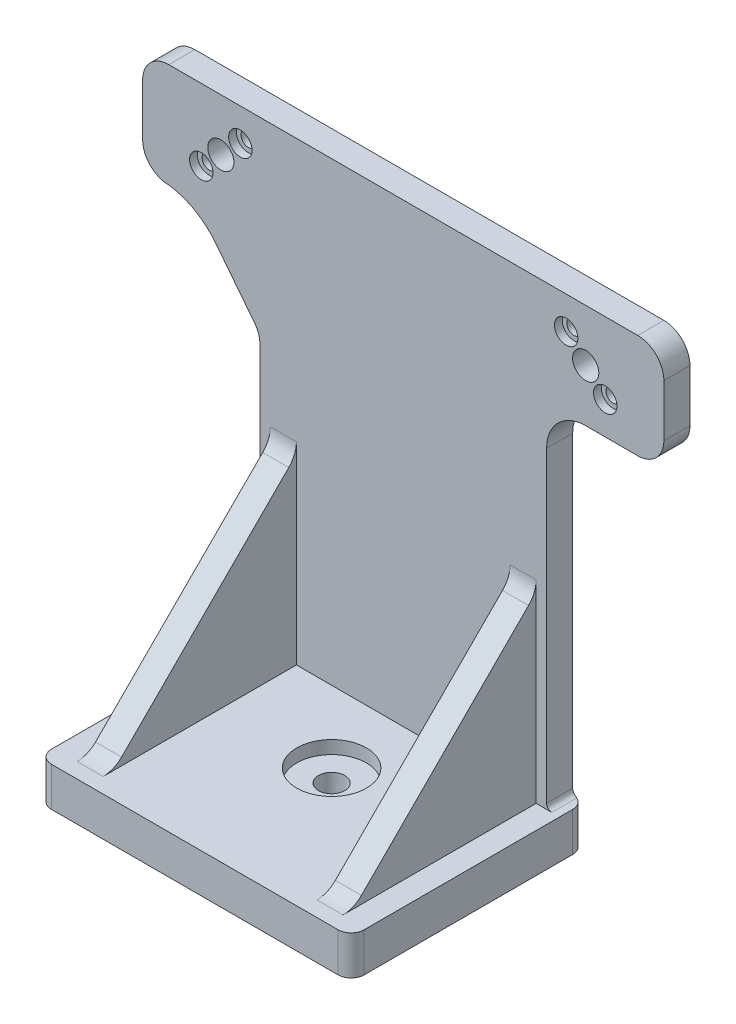
SolidWorks part; units mm, degrees
ref_plane "Ebene vorne" through (0, 0, 0) normal (0, 0, 1) x (1, 0, 0)
ref_plane "Ebene oben" through (0, 0, 0) normal (0, 1, 0) x (1, 0, 0)
ref_plane "Ebene rechts" through (0, 0, 0) normal (1, 0, 0) x (0, 0, -1)
sketch "Skizze1" plane through (0, 0, 0) normal (0, 0, 1) x (1, 0, 0)
  line L0 (0, 0) -> (0, 120.8446) construction
  line L1 (0, 120.8446) -> (0, -115.4537) construction
  line L15 (90, 107.0546) -> (-90, 107.0546)
  line L16 (-100, 97.0546) -> (-100, 77.0546)
  line L17 (-90, 67.0546) -> (-70, 67.0546)
  line L18 (-55, 52.0546) -> (-55, -67.9454)
  line L19 (-55, -67.9454) -> (-60, -67.9454)
  line L20 (-60, -67.9454) -> (-60, -82.9454)
  line L21 (-60, -82.9454) -> (60, -82.9454)
  line L22 (60, -67.9454) -> (60, -82.9454)
  line L23 (55, -67.9454) -> (60, -67.9454)
  line L24 (55, 52.0546) -> (55, -67.9454)
  line L25 (90, 67.0546) -> (70, 67.0546)
  line L26 (100, 97.0546) -> (100, 77.0546)
  line L32 (-152.8572, 87.0546) -> (12.8572, 87.0546) construction
  line L33 (-62.5, 94.5546) -> (-83.4096, 94.5546) construction
  line L34 (-77.5, 79.5546) -> (-83.4096, 79.5546) construction
  line L35 (-62.5, 94.5546) -> (-62.5, 69.0538) construction
  line L36 (-77.5, 79.5546) -> (-77.5, 100.8525) construction
  line L38 (-55, -67.9454) -> (55, -67.9454) construction
  arc A0 (-100, 77.0546) -> (-90, 67.0546) centre (-90, 77.0546) ccw
  arc A1 (-90, 107.0546) -> (-100, 97.0546) centre (-90, 97.0546) ccw
  arc A2 (-70, 67.0546) -> (-55, 52.0546) centre (-70, 52.0546) cw
  arc A3 (70, 67.0546) -> (55, 52.0546) centre (70, 52.0546) ccw
  arc A4 (90, 107.0546) -> (100, 97.0546) centre (90, 97.0546) cw
  arc A5 (100, 77.0546) -> (90, 67.0546) centre (90, 77.0546) cw
  circle A10 centre (-70, 87.0546) radius 5.025
  circle A11 centre (-62.5, 94.5546) radius 2.75
  circle A12 centre (-77.5, 79.5546) radius 2.75
  circle A13 centre (77.5, 79.5546) radius 2.75
  circle A14 centre (62.5, 94.5546) radius 2.75
  circle A15 centre (70, 87.0546) radius 5.025
  point P18 (-100, 107.0546)
  point P22 (0, 107.0546)
  point P23 (0, -82.9454)
  point P33 (100, 107.0546)
  point P50 (0, -29.2954)
  point P51 (0, 33.7046)
  dimension "D7" = 10
  dimension "D8" = 15
  dimension "D15" = 10.05
  dimension "D16" = 5.5
  dimension "D17" = 5.5
  dimension "D1" = 100
  dimension "D2" = 55
  dimension "D3" = 60
  dimension "D4" = 40
  dimension "D5" = 135
  dimension "D6" = 15
  dimension "D18" = 7.5
  dimension "D19" = 7.5
  dimension "D20" = 7.5
  dimension "D21" = 7.5
  dimension "D22" = 20
  dimension "D23" = 140
extrude "Aufsatz-Linear austragen1" add sketch "Skizze1" along normal blind 10
sketch "Skizze2" plane through (0, 0, 10) normal (0, 0, 1) x (1, 0, 0)
  line L0 (-21.55, 2.2046) -> (21.55, 2.2046) construction
  line L3 (0, 33.7046) -> (0, -29.2954) construction
  line L6 (-70, 92.0796) -> (-70, 82.0296) construction
  line L7 (-64.975, 87.0546) -> (-75.025, 87.0546) construction
  line L8 (-13.4991, -8.9319) -> (-83.4991, 75.9181)
  line L9 (-56.5009, 98.1912) -> (13.4991, 13.3412)
  circle A0 centre (-70, 87.0546) radius 5.025 construction
  circle A1 centre (0, 2.2046) radius 17.5
  circle A2 centre (-70, 87.0546) radius 17.5
  point P2 (0, 0)
  point P3 (0, 0)
  point P27 (0, 0)
  point P28 (0, 0)
  point P29 (0, 0)
  dimension "D1" = 35
  dimension "D2" = 35
sketch "Skizze3" plane through (0, 0, 10) normal (0, 0, 1) x (1, 0, 0)
  line L0 (-90, 67.0546) -> (-70, 67.0546) construction
  line L1 (-72.8459, 57.8146) -> (-56.7743, 37.3523)
  line L2 (-55, 52.0546) -> (-55, -67.9454) construction
  line L3 (-55, 18.961) -> (-43.3334, 21.2005)
  line L4 (-43.3334, 21.2005) -> (-45.498, 67.0546)
  line L5 (-45.498, 67.0546) -> (-90, 67.0546)
  arc A0 (-100, 77.0546) -> (-90, 67.0546) centre (-90, 77.0546) ccw construction
  spline S0 degree 2 poles (-90, 67.0546) (-79.9383, 65.6564) (-72.8459, 57.8146) knots 0 0 0 1 1 1
  spline S1 degree 2 poles (-55, 18.961) (-46.6365, 27.9631) (-56.7743, 37.3523) knots 0 0 0 1 1 1
extrude "Aufsatz-Linear austragen3" add sketch "Skizze3" against normal blind 10
sketch "Skizze4" plane through (0, 0, 10) normal (0, 0, 1) x (1, 0, 0)
  line L1 (-60, -67.9454) -> (60, -67.9454)
  line L2 (-60, -67.9454) -> (-60, -82.9454)
  line L3 (-60, -82.9454) -> (60, -82.9454)
  line L4 (60, -67.9454) -> (60, -82.9454)
extrude "Aufsatz-Linear austragen4" add sketch "Skizze4" along normal blind 80
sketch "Skizze6" plane through (-55, 0, 0) normal (-1, 0, 0) x (0, 0, 1)
  line L5 (60.1366, -67.0551) -> (60.1366, -66.9447)
ref_plane "Ebene1" through (-51, 0, 0) normal (-1, 0, 0) x (0, 0, 1)
sketch "Skizze9" plane through (-51, 0, 0) normal (-1, 0, 0) x (0, 0, 1)
  line L0 (10, 2.0546) -> (80, -67.9454)
  line L1 (10, 35.555) -> (10, -67.9454) construction
  line L2 (90, -67.9454) -> (0, -67.9454) construction
  line L3 (80, -67.9454) -> (6.6442, -67.9454)
  line L4 (10, -67.9454) -> (0, -67.9454) construction
  line L5 (6.6442, -67.9454) -> (6.6442, 2.0546)
  line L6 (6.6442, 2.0546) -> (10, 2.0546)
  dimension "D1" = 70
  dimension "D2" = 70
extrude "Aufsatz-Linear austragen5" add sketch "Skizze9" against normal blind 10
ref_plane "Ebene2" through (51, 0, 0) normal (1, 0, 0) x (0, 0, -1)
sketch "Skizze10" plane through (51, 0, 0) normal (1, 0, 0) x (0, 0, -1)
  line L0 (-10, 2.2046) -> (-80, -67.9454)
  line L1 (-10, 19.7046) -> (-10, -15.2954) construction
  line L2 (-80, -67.9454) -> (-10, -67.9454)
  line L3 (-90, -67.9454) -> (0, -67.9454) construction
  line L4 (-80, -67.9454) -> (-10, -67.9454) construction
  line L5 (-10, -67.9454) -> (-10, 2.2046)
extrude "Aufsatz-Linear austragen6" add sketch "Skizze10" against normal blind 10
fillet "Verrundung3" radius 10 4 edges at (-46, -67.9454, 80) (46, -67.9454, 80) (46, 2.2046, 10) (-46, 2.0546, 10)
fillet "Verrundung4" radius 5 4 edges at (-60, -75.4454, 90) (60, -75.4454, 90) (60, -75.4454, 0) (-60, -75.4454, 0)
fillet "Verrundung5" radius 10 1 edges at (-55, 35.555, 5)
sketch "Skizze11" plane through (0, 0, 10) normal (0, 0, 1) x (1, 0, 0)
  circle A0 centre (62.5, 94.5546) radius 4.5
  circle A2 centre (77.5, 79.5546) radius 4.5
  circle A3 centre (-62.5, 94.5546) radius 4.5
  circle A4 centre (-77.5, 79.5546) radius 4.5
  dimension "D1" = 9
  dimension "D2" = 9
  dimension "D3" = 9
  dimension "D4" = 9
extrude "Schnitt-Linear austragen1" cut sketch "Skizze11" against normal blind 3
fillet "Verrundung6" radius 2 2 edges at (55, -67.9454, 5) (-55, -67.9454, 5)
sketch "Skizze13" plane through (0, -67.9454, 0) normal (0, 1, 0) x (1, 0, 0)
  line L0 (-17.5, -10) -> (17.5, -10) construction
  line L1 (0, 0) -> (0, -90) construction
  line L2 (55, -90) -> (-55, -90) construction
  circle A0 centre (0, -37.5) radius 5.05
  dimension "D1" = 10.1
  dimension "D2" = 27.5
extrude "Schnitt-Linear austragen3" cut sketch "Skizze13" against normal through all
sketch "Skizze14" plane through (0, -67.9454, 0) normal (0, 1, 0) x (1, 0, 0)
  circle A0 centre (0, -37.5) radius 13.3825
  dimension "D1" = 26.765
extrude "Schnitt-Linear austragen4" cut sketch "Skizze14" against normal blind 5 contours A0
equation "\"D1@Skizze13\"=10*1.01"
